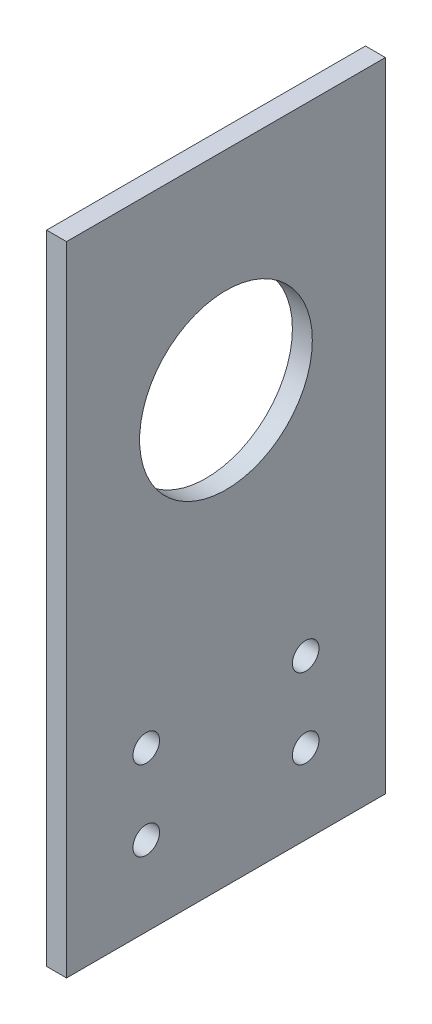
SolidWorks part; units mm, degrees
material "6061 Alloy"
ref_plane "Front Plane" through (0, 0, 0) normal (0, 0, 1) x (1, 0, 0)
ref_plane "Top Plane" through (0, 0, 0) normal (0, 1, 0) x (1, 0, 0)
ref_plane "Right Plane" through (0, 0, 0) normal (1, 0, 0) x (0, 0, -1)
sketch "Sketch1" plane through (0, 0, 0) normal (1, 0, 0) x (0, 0, -1)
  line L1 (-38.1, 76.2) -> (38.1, 76.2)
  line L2 (-38.1, 76.2) -> (-38.1, -76.2)
  line L3 (-38.1, -76.2) -> (38.1, -76.2)
  line L4 (38.1, 76.2) -> (38.1, -76.2)
  line L5 (-38.1, 76.2) -> (38.1, -76.2) construction
  line L6 (-38.1, -76.2) -> (38.1, 76.2) construction
  point P0 (0, 0)
  dimension "D1" = 152.4
  dimension "D2" = 76.2
extrude "Boss-Extrude1" add sketch "Sketch1" along normal blind 4.7625
sketch "Sketch2" plane through (4.7625, 0, 0) normal (1, 0, 0) x (0, 0, -1)
  line L0 (-38.1, -76.2) -> (38.1, -76.2) construction
  line L1 (-38.1, 76.2) -> (-38.1, -76.2) construction
  circle A0 centre (0, 26.416) radius 20.6375
  dimension "D1" = 102.616
  dimension "D2" = 38.1
  dimension "D3" = 41.275
extrude "Cut-Extrude1" cut sketch "Sketch2" against normal up to next
sketch "Sketch4" plane through (4.7625, 0, 0) normal (1, 0, 0) x (0, 0, -1)
  line L0 (-38.1, 76.2) -> (-38.1, -76.2) construction
  line L1 (-38.1, -76.2) -> (38.1, -76.2) construction
  circle A0 centre (-19.05, -38.1) radius 3.175
  circle A1 centre (19.05, -38.1) radius 3.175
  circle A2 centre (19.05, -57.15) radius 3.175
  circle A3 centre (-19.05, -57.15) radius 3.175
  dimension "D1" = 19.05
  dimension "D2" = 6.35
  dimension "D3" = 38.1
  dimension "D5" = 2
  dimension "D4" = 2
extrude "Cut-Extrude2" cut sketch "Sketch4" against normal up to next
